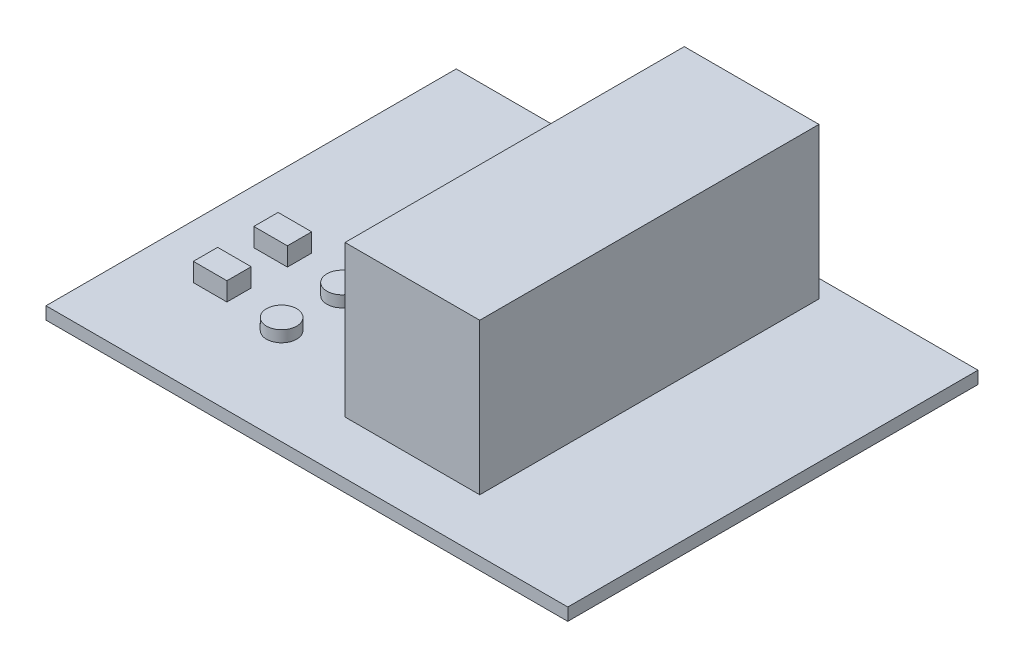
SolidWorks part; units mm, degrees
ref_plane "Front Plane" through (0, 0, 0) normal (0, 0, 1) x (1, 0, 0)
ref_plane "Top Plane" through (0, 0, 0) normal (0, 1, 0) x (1, 0, 0)
ref_plane "Right Plane" through (0, 0, 0) normal (1, 0, 0) x (0, 0, -1)
sketch "Sketch1" plane through (0, 0, 0) normal (0, 1, 0) x (1, 0, 0)
  line L1 (-34.515, -27.135) -> (34.515, -27.135)
  line L2 (-34.515, -27.135) -> (-34.515, 27.135)
  line L3 (-34.515, 27.135) -> (34.515, 27.135)
  line L4 (34.515, -27.135) -> (34.515, 27.135)
  line L5 (-34.515, -27.135) -> (34.515, 27.135) construction
  line L6 (-34.515, 27.135) -> (34.515, -27.135) construction
  point P0 (0, 0)
  dimension "D1" = 69.03
  dimension "D2" = 54.27
extrude "Boss-Extrude1" add sketch "Sketch1" along normal blind 1.65
sketch "Sketch2" plane through (0, 1.65, 0) normal (0, 1, 0) x (1, 0, 0)
  line L0 (-34.515, 27.135) -> (-34.515, -27.135) construction
  line L2 (-34.515, -27.135) -> (34.515, -27.135) construction
  line L5 (34.515, 27.135) -> (-34.515, 27.135) construction
  circle A0 centre (-16.095, -14.385) radius 2
  circle A1 centre (-16.095, -6.385) radius 2
  dimension "D1" = 18.42
  dimension "D3" = 8
  dimension "D2" = 12.75
extrude "Boss-Extrude2" add sketch "Sketch2" along normal blind 1.5
sketch "Sketch3" plane through (0, 1.65, 0) normal (0, 1, 0) x (1, 0, 0)
  line L0 (-34.515, -27.135) -> (34.515, -27.135) construction
  line L1 (-27.415, -11.53) -> (-22.975, -11.53)
  line L2 (-27.415, -11.53) -> (-27.415, -14.74)
  line L3 (-27.415, -14.74) -> (-22.975, -14.74)
  line L4 (-22.975, -11.53) -> (-22.975, -14.74)
  line L5 (-27.415, -11.53) -> (-22.975, -14.74) construction
  line L6 (-27.415, -14.74) -> (-22.975, -11.53) construction
  line L7 (-34.515, 27.135) -> (-34.515, -27.135) construction
  line L9 (-27.415, -3.53) -> (-22.975, -3.53)
  line L10 (-27.415, -3.53) -> (-27.415, -6.74)
  line L11 (-27.415, -6.74) -> (-22.975, -6.74)
  line L12 (-22.975, -3.53) -> (-22.975, -6.74)
  line L13 (-27.415, -3.53) -> (-22.975, -6.74) construction
  line L14 (-27.415, -6.74) -> (-22.975, -3.53) construction
  point P0 (-25.195, -13.135)
  point P10 (-25.195, -5.135)
  dimension "D1" = 14
  dimension "D2" = 9.32
  dimension "D3" = 4.44
  dimension "D4" = 3.21
  dimension "D5" = 3.21
  dimension "D6" = 4.44
  dimension "D7" = 8
extrude "Boss-Extrude3" add sketch "Sketch3" along normal blind 2.44
sketch "Sketch4" plane through (0, 1.65, 0) normal (0, 1, 0) x (1, 0, 0)
  line L0 (34.515, -27.135) -> (34.515, 27.135) construction
  line L1 (-1.985, 24.775) -> (15.835, 24.775)
  line L2 (-1.985, 24.775) -> (-1.985, -20.105)
  line L3 (-1.985, -20.105) -> (15.835, -20.105)
  line L4 (15.835, 24.775) -> (15.835, -20.105)
  line L5 (-34.515, -27.135) -> (34.515, -27.135) construction
  dimension "D1" = 17.82
  dimension "D2" = 44.88
  dimension "D3" = 18.68
  dimension "D4" = 7.03
extrude "Boss-Extrude4" add sketch "Sketch4" along normal blind 20
